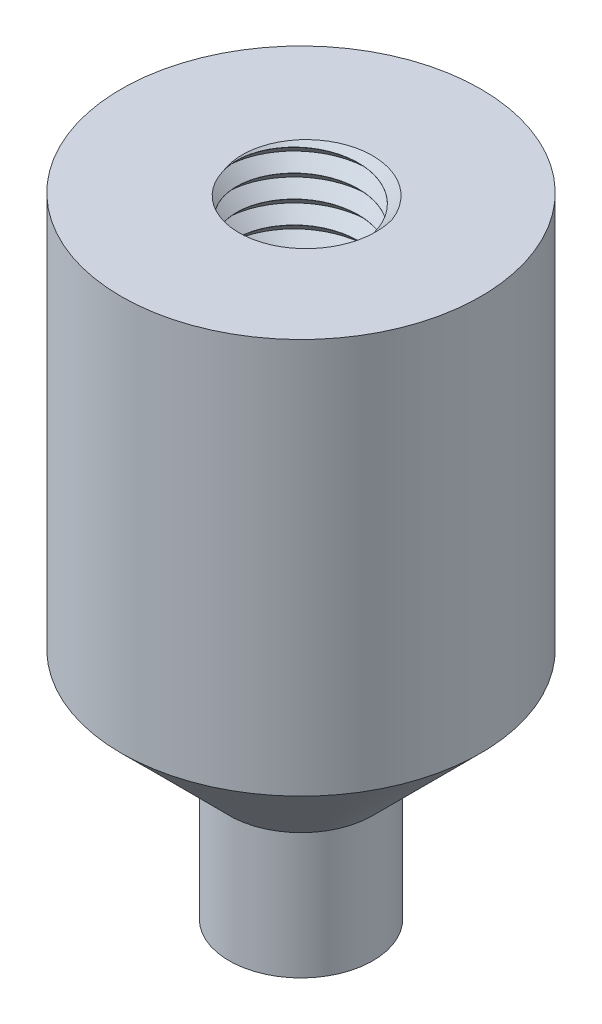
SolidWorks part; units mm, degrees
other "Markup1"
sketch "Sketch7" plane through (8, -40.1821, 8) normal (0.788, -0.5726, 0.226) x (0.2068, -0.0996, -0.9733)
other "Markup2"
sketch "Sketch8" plane through (10, -42.1821, -10) normal (0.2153, -0.7341, -0.6439) x (-0.8854, 0.1314, -0.4459)
material "7075-T6，板材(SS)"
ref_plane "前视基准面" through (0, 0, 0) normal (0, 0, 1) x (1, 0, 0)
ref_plane "上视基准面" through (0, 0, 0) normal (0, 1, 0) x (1, 0, 0)
ref_plane "右视基准面" through (0, 0, 0) normal (1, 0, 0) x (0, 0, -1)
sketch "草图1" plane through (0, 0, 0) normal (0, 0, 1) x (1, 0, 0)
  line L0 (0, 16.878) -> (0, -16.878) construction
  line L1 (0, 0) -> (3.4, 0) construction
  line L3 (3.4, 0) -> (10, 0)
  line L4 (3.4, 0) -> (3.4, -11)
  line L5 (3.4, -11) -> (10, -11)
  line L6 (10, 0) -> (10, -11)
  point P4 (0, 0)
  dimension "D1" = 3.4
  dimension "D2" = 10
  dimension "D3" = 11
revolve "旋转1" add sketch "草图1" angle 360 about L0
sketch "草图2" plane through (0, -11, 0) normal (0, -1, 0) x (1, 0, 0)
  circle A0 centre (0, 0) radius 3.4 construction
  circle A1 centre (0, 0) radius 3.4
curve "螺旋线/涡状线1" pitch 1.25 height 12.8125 radius 3.4 centre (0, -11, 0) axis (0, 1, 0) start towards (0, 0, -1)
sketch "草图3" plane through (0, 0, 0) normal (1, 0, 0) x (0, 0, -1)
  line L0 (3.4, -11.62) -> (3.4, -10.38)
  line L1 (3.4, -10.38) -> (4.025, -11)
  line L2 (-10, -11) -> (10, -11) construction
  line L3 (0, 0) -> (0, -13.2999) construction
  line L4 (-10, -11) -> (10, -11) construction
  line L5 (3.4, -11.62) -> (4.025, -11)
  spline S0 degree 3 poles (-996.1726, 15.4126) (-137.096, -13.3402) (13.9475, -12.0284) (2.4668, -10.8438) (1.335, -10.7656) (0, -10.6875) (-1.335, -10.6094) (-2.4668, -10.5313) (-3.223, -10.4531) (-3.4885, -10.375) (-3.223, -10.2969) (-2.4668, -10.2188) (-0.9577, -10.1146) (0.9577, -10.0104) (2.4668, -9.9063) (3.223, -9.8281) (3.4885, -9.75) (3.223, -9.6719) (2.4668, -9.5938) (0.9577, -9.4896) (-0.9577, -9.3854) (-2.4668, -9.2812) (-3.223, -9.2031) (-3.4885, -9.125) (-3.223, -9.0469) (-2.4668, -8.9687) (-0.9577, -8.8646) (0.9577, -8.7604) (2.4668, -8.6562) (3.223, -8.5781) (3.4885, -8.5) (3.223, -8.4219) (2.4668, -8.3437) (0.9577, -8.2396) (-0.9577, -8.1354) (-2.4668, -8.0312) (-3.223, -7.9531) (-3.4885, -7.875) (-3.223, -7.7969) (-2.4668, -7.7187) (-0.9577, -7.6146) (0.9577, -7.5104) (2.4668, -7.4062) (3.223, -7.3281) (3.4885, -7.25) (3.223, -7.1719) (2.4668, -7.0937) (0.9577, -6.9896) (-0.9577, -6.8854) (-2.4668, -6.7812) (-3.223, -6.7031) (-3.4885, -6.625) (-3.223, -6.5469) (-2.4668, -6.4687) (-0.9577, -6.3646) (0.9577, -6.2604) (2.4668, -6.1562) (3.223, -6.0781) (3.4885, -6) (3.223, -5.9219) (2.4668, -5.8437) (0.9577, -5.7396) (-0.9577, -5.6354) (-2.4668, -5.5312) (-3.223, -5.4531) (-3.4885, -5.375) (-3.223, -5.2969) (-2.4668, -5.2187) (-0.9577, -5.1146) (0.9577, -5.0104) (2.4668, -4.9062) (3.223, -4.8281) (3.4885, -4.75) (3.223, -4.6719) (2.4668, -4.5937) (0.9577, -4.4896) (-0.9577, -4.3854) (-2.4668, -4.2812) (-3.223, -4.2031) (-3.4885, -4.125) (-3.223, -4.0469) (-2.4668, -3.9687) (-0.9577, -3.8646) (0.9577, -3.7604) (2.4668, -3.6562) (3.223, -3.5781) (3.4885, -3.5) (3.223, -3.4219) (2.4668, -3.3437) (0.9577, -3.2396) (-0.9577, -3.1354) (-2.4668, -3.0312) (-3.223, -2.9531) (-3.4885, -2.875) (-3.223, -2.7969) (-2.4668, -2.7187) (-0.9577, -2.6146) (0.9577, -2.5104) (2.4668, -2.4062) (3.223, -2.3281) (3.4885, -2.25) (3.223, -2.1719) (2.4668, -2.0937) (0.9577, -1.9896) (-0.9577, -1.8854) (-2.4668, -1.7812) (-3.223, -1.7031) (-3.4885, -1.625) (-3.223, -1.5469) (-2.4668, -1.4687) (-0.9577, -1.3646) (0.9577, -1.2604) (2.4668, -1.1562) (3.223, -1.0781) (3.4885, -1) (3.223, -0.9219) (2.4668, -0.8437) (0.9577, -0.7396) (-0.9577, -0.6354) (-2.4668, -0.5312) (-3.223, -0.4531) (-3.4885, -0.375) (-3.223, -0.2969) (-2.4668, -0.2187) (-0.9577, -0.1146) (0.9577, -0.0104) (2.4668, 0.0938) (3.223, 0.1719) (3.4885, 0.25) (3.223, 0.3281) (2.4668, 0.4063) (0.9577, 0.5104) (-0.9577, 0.6146) (-2.4668, 0.7188) (-3.223, 0.7969) (-3.4885, 0.875) (-3.223, 0.9531) (-2.4668, 1.0313) (-0.9577, 1.1354) (0.9577, 1.2396) (2.4668, 1.3438) (3.223, 1.4219) (3.4885, 1.5) (3.2231, 1.5781) (2.4664, 1.6563) (-9.7756, 2.5015) (-56.5284, 3.3973) (999.7956, -6.0316) knots -0.259424 -0.259424 -0.259424 -0.259424 0.006098 0.012195 0.018293 0.02439 0.030488 0.036585 0.042683 0.04878 0.054878 0.060976 0.067073 0.079268 0.085366 0.091463 0.097561 0.103659 0.109756 0.115854 0.128049 0.134146 0.140244 0.146341 0.152439 0.158537 0.164634 0.176829 0.182927 0.189024 0.195122 0.20122 0.207317 0.213415 0.22561 0.231707 0.237805 0.243902 0.25 0.256098 0.262195 0.27439 0.280488 0.286585 0.292683 0.29878 0.304878 0.310976 0.323171 0.329268 0.335366 0.341463 0.347561 0.353659 0.359756 0.371951 0.378049 0.384146 0.390244 0.396341 0.402439 0.408537 0.420732 0.426829 0.432927 0.439024 0.445122 0.45122 0.457317 0.469512 0.47561 0.481707 0.487805 0.493902 0.5 0.506098 0.518293 0.52439 0.530488 0.536585 0.542683 0.54878 0.554878 0.567073 0.573171 0.579268 0.585366 0.591463 0.597561 0.603659 0.615854 0.621951 0.628049 0.634146 0.640244 0.646341 0.652439 0.664634 0.670732 0.676829 0.682927 0.689024 0.695122 0.70122 0.713415 0.719512 0.72561 0.731707 0.737805 0.743902 0.75 0.762195 0.768293 0.77439 0.780488 0.786585 0.792683 0.79878 0.810976 0.817073 0.823171 0.829268 0.835366 0.841463 0.847561 0.859756 0.865854 0.871951 0.878049 0.884146 0.890244 0.896341 0.908537 0.914634 0.920732 0.926829 0.932927 0.939024 0.945122 0.957317 0.963415 0.969512 0.97561 0.981707 0.987805 0.993902 1.179862 1.179862 1.179862 1.179862 only from (3.4, -11) to (0, 1.8125) construction
  spline S1 degree 3 poles (3.4, -11) (3.4, -10.9741) (3.223, -10.9218) (2.4668, -10.8438) (1.335, -10.7656) (0, -10.6875) (-1.335, -10.6094) (-2.4668, -10.5313) (-3.223, -10.4531) (-3.4885, -10.375) (-3.223, -10.2969) (-2.4668, -10.2188) (-0.9577, -10.1146) (0.9577, -10.0104) (2.4668, -9.9063) (3.223, -9.8281) (3.4885, -9.75) (3.223, -9.6719) (2.4668, -9.5938) (0.9577, -9.4896) (-0.9577, -9.3854) (-2.4668, -9.2812) (-3.223, -9.2031) (-3.4885, -9.125) (-3.223, -9.0469) (-2.4668, -8.9687) (-0.9577, -8.8646) (0.9577, -8.7604) (2.4668, -8.6562) (3.223, -8.5781) (3.4885, -8.5) (3.223, -8.4219) (2.4668, -8.3437) (0.9577, -8.2396) (-0.9577, -8.1354) (-2.4668, -8.0312) (-3.223, -7.9531) (-3.4885, -7.875) (-3.223, -7.7969) (-2.4668, -7.7187) (-0.9577, -7.6146) (0.9577, -7.5104) (2.4668, -7.4062) (3.223, -7.3281) (3.4885, -7.25) (3.223, -7.1719) (2.4668, -7.0937) (0.9577, -6.9896) (-0.9577, -6.8854) (-2.4668, -6.7812) (-3.223, -6.7031) (-3.4885, -6.625) (-3.223, -6.5469) (-2.4668, -6.4687) (-0.9577, -6.3646) (0.9577, -6.2604) (2.4668, -6.1562) (3.223, -6.0781) (3.4885, -6) (3.223, -5.9219) (2.4668, -5.8437) (0.9577, -5.7396) (-0.9577, -5.6354) (-2.4668, -5.5312) (-3.223, -5.4531) (-3.4885, -5.375) (-3.223, -5.2969) (-2.4668, -5.2187) (-0.9577, -5.1146) (0.9577, -5.0104) (2.4668, -4.9062) (3.223, -4.8281) (3.4885, -4.75) (3.223, -4.6719) (2.4668, -4.5937) (0.9577, -4.4896) (-0.9577, -4.3854) (-2.4668, -4.2812) (-3.223, -4.2031) (-3.4885, -4.125) (-3.223, -4.0469) (-2.4668, -3.9687) (-0.9577, -3.8646) (0.9577, -3.7604) (2.4668, -3.6562) (3.223, -3.5781) (3.4885, -3.5) (3.223, -3.4219) (2.4668, -3.3437) (0.9577, -3.2396) (-0.9577, -3.1354) (-2.4668, -3.0312) (-3.223, -2.9531) (-3.4885, -2.875) (-3.223, -2.7969) (-2.4668, -2.7187) (-0.9577, -2.6146) (0.9577, -2.5104) (2.4668, -2.4062) (3.223, -2.3281) (3.4885, -2.25) (3.223, -2.1719) (2.4668, -2.0937) (0.9577, -1.9896) (-0.9577, -1.8854) (-2.4668, -1.7812) (-3.223, -1.7031) (-3.4885, -1.625) (-3.223, -1.5469) (-2.4668, -1.4687) (-0.9577, -1.3646) (0.9577, -1.2604) (2.4668, -1.1562) (3.223, -1.0781) (3.4885, -1) (3.223, -0.9219) (2.4668, -0.8437) (0.9577, -0.7396) (-0.9577, -0.6354) (-2.4668, -0.5312) (-3.223, -0.4531) (-3.4885, -0.375) (-3.223, -0.2969) (-2.4668, -0.2187) (-0.9577, -0.1146) (0.9577, -0.0104) (2.4668, 0.0938) (3.223, 0.1719) (3.4885, 0.25) (3.223, 0.3281) (2.4668, 0.4063) (0.9577, 0.5104) (-0.9577, 0.6146) (-2.4668, 0.7188) (-3.223, 0.7969) (-3.4885, 0.875) (-3.223, 0.9531) (-2.4668, 1.0313) (-0.9577, 1.1354) (0.9577, 1.2396) (2.4668, 1.3438) (3.223, 1.4219) (3.4885, 1.5) (3.2231, 1.5781) (2.4664, 1.6563) (1.3363, 1.7343) (0.4422, 1.7866) (0, 1.8125) knots 0 0 0 0 0.006098 0.012195 0.018293 0.02439 0.030488 0.036585 0.042683 0.04878 0.054878 0.060976 0.067073 0.079268 0.085366 0.091463 0.097561 0.103659 0.109756 0.115854 0.128049 0.134146 0.140244 0.146341 0.152439 0.158537 0.164634 0.176829 0.182927 0.189024 0.195122 0.20122 0.207317 0.213415 0.22561 0.231707 0.237805 0.243902 0.25 0.256098 0.262195 0.27439 0.280488 0.286585 0.292683 0.29878 0.304878 0.310976 0.323171 0.329268 0.335366 0.341463 0.347561 0.353659 0.359756 0.371951 0.378049 0.384146 0.390244 0.396341 0.402439 0.408537 0.420732 0.426829 0.432927 0.439024 0.445122 0.45122 0.457317 0.469512 0.47561 0.481707 0.487805 0.493902 0.5 0.506098 0.518293 0.52439 0.530488 0.536585 0.542683 0.54878 0.554878 0.567073 0.573171 0.579268 0.585366 0.591463 0.597561 0.603659 0.615854 0.621951 0.628049 0.634146 0.640244 0.646341 0.652439 0.664634 0.670732 0.676829 0.682927 0.689024 0.695122 0.70122 0.713415 0.719512 0.72561 0.731707 0.737805 0.743902 0.75 0.762195 0.768293 0.77439 0.780488 0.786585 0.792683 0.79878 0.810976 0.817073 0.823171 0.829268 0.835366 0.841463 0.847561 0.859756 0.865854 0.871951 0.878049 0.884146 0.890244 0.896341 0.908537 0.914634 0.920732 0.926829 0.932927 0.939024 0.945122 0.957317 0.963415 0.969512 0.97561 0.981707 0.987805 0.993902 1 1 1 1 construction
  dimension "D1" = 4.025
  dimension "D2" = 0.62
sweep "切除-扫描1" cut profiles "草图3" path "螺旋线/涡状线1" align with end faces yes
sketch "草图4" plane through (0, 0, 0) normal (0, 0, 1) x (1, 0, 0)
  line L0 (-10, -11) -> (10, -11) construction
  line L1 (-10, -11) -> (10, -11) construction
  line L2 (0, 0) -> (0, -14.1821) construction
  line L3 (0, -13.3238) -> (4.025, -11)
  line L4 (4.025, -11) -> (10, -11)
  line L10 (0, -13.3238) -> (0, -14.1821)
  line L14 (10, -11) -> (10, -14.1821)
  line L15 (10, -14.1821) -> (0, -14.1821)
  dimension "D1" = 4.025
  dimension "D2" = 60
revolve "旋转2" add sketch "草图4" angle 360 about L2
sketch "Sketch9" plane through (0, -14.1821, 0) normal (0, -1, 0) x (1, 0, 0)
  circle A1 centre (0, 0) radius 10
  circle A2 centre (0, 0) radius 10
  dimension "D1" = 0
extrude "Boss-Extrude2" add sketch "Sketch9" along normal blind 0.82
sketch "Sketch10" plane through (0, 0, 0) normal (1, 0, 0) x (0, 0, -1)
  line L0 (-10, -15.0021) -> (-10, -22.0021)
  line L7 (-10, -15.0021) -> (10, -15.0021) construction
  line L8 (0, -15.0021) -> (-10, -15.0021)
  line L16 (-4, -28.0021) -> (-10, -22.0021)
  line L17 (-4, -28.0021) -> (-4, -35.0021)
  line L18 (-4, -35.0021) -> (0, -35.0021)
  line L19 (0, -35.0021) -> (0, -15.0021)
  point P4 (0, 0)
  point P7 (-5.0803, -27.9057)
  dimension "D1" = 7
  dimension "D2" = 7
  dimension "D3" = 6
  dimension "D4" = 6
revolve "Revolve1" add sketch "Sketch10" angle 360 about L19
